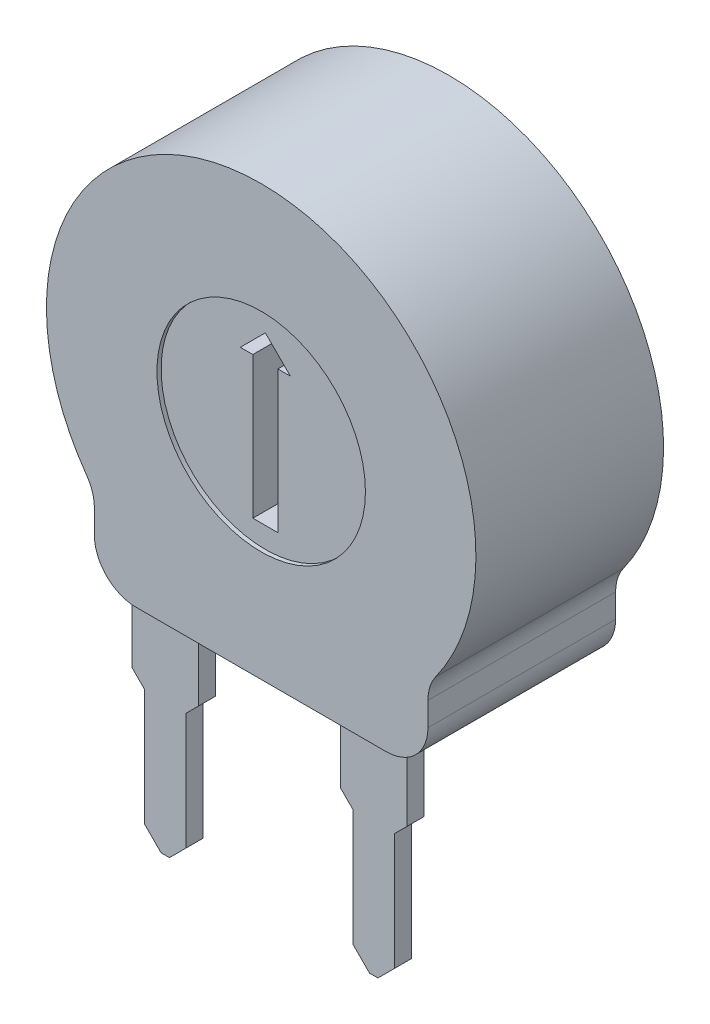
SolidWorks part; units mm, degrees
ref_plane "Plan de face" through (0, 0, 0) normal (0, 0, 1) x (1, 0, 0)
ref_plane "Plan de dessus" through (0, 0, 0) normal (0, 1, 0) x (1, 0, 0)
ref_plane "Plan de droite" through (0, 0, 0) normal (1, 0, 0) x (0, 0, -1)
sketch "Esquisse1" plane through (0, 0, 0) normal (0, 0, 1) x (1, 0, 0)
  line L0 (-4, -3.2438) -> (-4, -5.15)
  line L1 (-4, -5.15) -> (4, -5.15)
  line L2 (4, -5.15) -> (4, -3.2438)
  arc A0 (-4, -3.2438) -> (4, -3.2438) centre (0, 0) cw
  dimension "D1" = 5.15
  dimension "D2" = 5.15
  dimension "D3" = 8
extrude "Boss.-Extru.1" add sketch "Esquisse1" along normal blind 4.5
sketch "Esquisse2" plane through (0, -5.15, 0) normal (0, -1, 0) x (1, 0, 0)
  line L0 (0, 0) -> (0, 1.6) construction
  line L1 (-3.3, 3.9) -> (-1.7, 3.9)
  line L2 (-3.3, 3.9) -> (-3.3, 4.3)
  line L3 (-3.3, 4.3) -> (-1.7, 4.3)
  line L4 (-1.7, 3.9) -> (-1.7, 4.3)
  line L5 (-3.3, 3.9) -> (-1.7, 4.3) construction
  line L6 (-3.3, 4.3) -> (-1.7, 3.9) construction
  line L7 (1.7, 3.9) -> (3.3, 3.9)
  line L8 (1.7, 3.9) -> (1.7, 4.3)
  line L9 (1.7, 4.3) -> (3.3, 4.3)
  line L10 (3.3, 3.9) -> (3.3, 4.3)
  line L11 (1.7, 3.9) -> (3.3, 4.3) construction
  line L12 (1.7, 4.3) -> (3.3, 3.9) construction
  line L13 (-0.8, 1.4) -> (0.8, 1.4)
  line L14 (-0.8, 1.4) -> (-0.8, 1.8)
  line L15 (-0.8, 1.8) -> (0.8, 1.8)
  line L16 (0.8, 1.4) -> (0.8, 1.8)
  line L17 (-0.8, 1.4) -> (0.8, 1.8) construction
  line L18 (-0.8, 1.8) -> (0.8, 1.4) construction
  line L19 (-4, 4.5) -> (4, 4.5) construction
  point P0 (-2.5, 4.1)
  point P5 (2.5, 4.1)
  point P10 (0, 1.6)
  dimension "D1" = 2.5
  dimension "D2" = 2.5
  dimension "D3" = 1.6
  dimension "D4" = 0.4
  dimension "D5" = 2.5
  dimension "D6" = 0.2
extrude "Boss.-Extru.2" add sketch "Esquisse2" along normal blind 1.5
sketch "Esquisse3" plane through (0, -6.65, 0) normal (0, -1, 0) x (1, 0, 0)
  line L0 (-1.7, 4.3) -> (-3.3, 4.3) construction
  line L1 (-3, 4.3) -> (-2, 4.3)
  line L2 (-3, 4.3) -> (-3, 3.9)
  line L3 (-3, 3.9) -> (-2, 3.9)
  line L4 (-2, 4.3) -> (-2, 3.9)
  line L5 (-3.3, 3.9) -> (-1.7, 3.9) construction
  line L6 (3.3, 4.3) -> (1.7, 4.3) construction
  line L7 (2, 4.3) -> (3, 4.3)
  line L8 (2, 4.3) -> (2, 3.9)
  line L9 (2, 3.9) -> (3, 3.9)
  line L10 (3, 4.3) -> (3, 3.9)
  line L11 (1.7, 3.9) -> (3.3, 3.9) construction
  line L12 (0.8, 1.8) -> (-0.8, 1.8) construction
  line L13 (-0.5, 1.8) -> (0.5, 1.8)
  line L14 (-0.5, 1.8) -> (-0.5, 1.4)
  line L15 (-0.5, 1.4) -> (0.5, 1.4)
  line L16 (0.5, 1.8) -> (0.5, 1.4)
  line L17 (-0.8, 1.4) -> (0.8, 1.4) construction
  line L18 (-3.3, 4.3) -> (-3.3, 3.9) construction
  line L19 (1.7, 4.3) -> (1.7, 3.9) construction
  line L20 (-0.8, 1.8) -> (-0.8, 1.4) construction
  dimension "D1" = 1
  dimension "D2" = 0.3
  dimension "D3" = 0.3
  dimension "D4" = 0.3
extrude "Boss.-Extru.3" add sketch "Esquisse3" along normal blind 3.5
chamfer "Chanfrein1" distance 0.3 angle 45 6 edges at (3, -6.65, 4.1) (-2, -6.65, 4.1) (0.5, -6.65, 1.6) (-0.5, -6.65, 1.6) (2, -6.65, 4.1) (-3, -6.65, 4.1)
chamfer "Chanfrein2" distance 0.4 angle 45 6 edges at (-0.5, -10.15, 1.6) (0.5, -10.15, 1.6) (3, -10.15, 4.1) (2, -10.15, 4.1) (-2, -10.15, 4.1) (-3, -10.15, 4.1)
sketch "Esquisse4" plane through (0, 0, 0) normal (0, 0, -1) x (-1, 0, 0)
  circle A0 centre (0, 0) radius 2.5
  dimension "D1" = 5
extrude "Enlèv. mat.-Extru.1" cut sketch "Esquisse4" against normal blind 0.1
sketch "Esquisse5" plane through (0, 0, 4.5) normal (0, 0, 1) x (1, 0, 0)
  circle A0 centre (0, 0) radius 2.5
  dimension "D1" = 5
extrude "Enlèv. mat.-Extru.2" cut sketch "Esquisse5" against normal blind 0.1
sketch "Esquisse6" plane through (0, 0, 0.1) normal (0, 0, -1) x (-1, 0, 0)
  line L0 (0, 2) -> (-0.6, 1.4)
  line L1 (-0.6, 1.4) -> (-0.3, 1.4)
  line L2 (-0.3, 1.4) -> (-0.3, -2)
  line L3 (-0.3, -2) -> (0.3, -2)
  line L4 (0.3, -2) -> (0.3, 1.4)
  line L5 (0.3, 1.4) -> (0.6, 1.4)
  line L6 (0.6, 1.4) -> (0, 2)
  dimension "D1" = 0.3
  dimension "D2" = 0.3
  dimension "D3" = 45
  dimension "D4" = 2
  dimension "D5" = 2
  dimension "D6" = 1.2
extrude "Enlèv. mat.-Extru.3" cut sketch "Esquisse6" against normal through all
fillet "Congé1" radius 1 4 edges at (-4, -3.2438, 2.25) (-4, -5.15, 2.25) (4, -3.2438, 2.25) (4, -5.15, 2.25)
